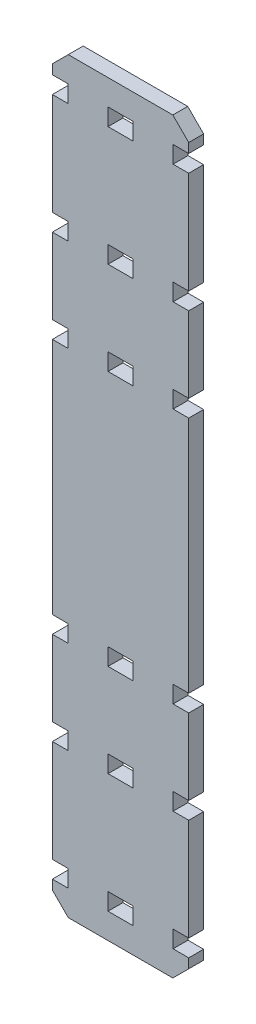
SolidWorks part; units mm, degrees
ref_plane "Front" through (0, 0, 0) normal (0, 0, 1) x (1, 0, 0)
ref_plane "Top" through (0, 0, 0) normal (0, 1, 0) x (1, 0, 0)
ref_plane "Right" through (0, 0, 0) normal (1, 0, 0) x (0, 0, -1)
ref_axis "side-side" through (80.9, 0, 0) along (-1, 0, 0)
ref_axis "up-down" through (0, 50, 0) along (0, -1, 0)
ref_axis "front-back" through (0, 0, -80.9) along (0, 0, 1)
sketch "Sketch1" plane through (0, 0, 0) normal (0, 0, 1) x (1, 0, 0)
  line L0 (21.7993, 111.361) -> (21.7993, 119.489) construction
  line L1 (43.5986, 119.489) -> (0, 119.489)
  line L2 (43.5986, 119.489) -> (43.5986, 111.361)
  line L3 (43.5986, -119.489) -> (0, -119.489)
  line L4 (0, 119.489) -> (0, 111.361)
  line L5 (25.7993, 111.361) -> (17.7993, 111.361)
  line L6 (5, 111.361) -> (-15, 111.361) construction
  line L7 (0, -111.361) -> (5, -111.361) construction
  line L8 (43.5986, 105.9) -> (38.5986, 105.9) construction
  line L9 (0, 111.361) -> (5, 111.361)
  line L10 (25.7993, 111.361) -> (25.7993, 105.9)
  line L11 (0, 105.9) -> (5, 105.9)
  line L12 (5, 111.361) -> (5, 105.9)
  line L13 (43.5986, 111.361) -> (38.5986, 111.361) construction
  line L14 (38.5986, 111.361) -> (43.5986, 111.361)
  line L15 (38.5986, 111.361) -> (38.5986, 105.9)
  line L16 (38.5986, 105.9) -> (43.5986, 105.9)
  line L17 (43.5986, 105.9) -> (43.5986, 73.261)
  line L18 (0, 105.9) -> (0, 73.261)
  line L19 (25.7993, 105.9) -> (17.7993, 105.9)
  line L20 (17.7993, 111.361) -> (17.7993, 105.9)
  line L21 (43.5986, 73.261) -> (38.5986, 73.261) construction
  line L22 (38.5986, 73.261) -> (43.5986, 73.261)
  line L23 (38.5986, 73.261) -> (38.5986, 67.8)
  line L24 (38.5986, 67.8) -> (43.5986, 67.8)
  line L25 (43.5986, 38.1) -> (43.5986, -38.1)
  line L26 (43.5986, 67.8) -> (38.5986, 67.8) construction
  line L27 (5, 73.261) -> (0, 73.261)
  line L28 (5, 73.261) -> (5, 67.8)
  line L29 (5, 67.8) -> (0, 67.8)
  line L31 (43.5986, 43.561) -> (38.5986, 43.561) construction
  line L32 (38.5986, 43.561) -> (43.5986, 43.561)
  line L33 (38.5986, 43.561) -> (38.5986, 38.1)
  line L34 (38.5986, 38.1) -> (43.5986, 38.1)
  line L35 (0, 67.8) -> (0, 43.561)
  line L36 (43.5986, 38.1) -> (38.5986, 38.1) construction
  line L37 (0, 43.561) -> (5, 43.561)
  line L39 (0, 38.1) -> (5, 38.1)
  line L40 (5, 43.561) -> (5, 38.1)
  line L41 (25.7993, 73.261) -> (17.7993, 73.261)
  line L42 (25.7993, 73.261) -> (25.7993, 67.8)
  line L43 (25.7993, 67.8) -> (17.7993, 67.8)
  line L44 (17.7993, 73.261) -> (17.7993, 67.8)
  line L45 (25.7993, 43.561) -> (17.7993, 43.561)
  line L46 (25.7993, 43.561) -> (25.7993, 38.1)
  line L47 (25.7993, 38.1) -> (17.7993, 38.1)
  line L48 (17.7993, 43.561) -> (17.7993, 38.1)
  line L49 (-15, -38.1) -> (5, -38.1) construction
  line L50 (38.5986, -38.1) -> (43.5986, -38.1)
  line L51 (38.5986, -38.1) -> (38.5986, -43.561)
  line L52 (38.5986, -43.561) -> (43.5986, -43.561)
  line L53 (0, -43.561) -> (0, -67.8)
  line L54 (-15, -67.8) -> (5, -67.8) construction
  line L55 (38.5986, -67.8) -> (43.5986, -67.8)
  line L56 (38.5986, -67.8) -> (38.5986, -73.261)
  line L57 (38.5986, -73.261) -> (43.5986, -73.261)
  line L58 (43.5986, -43.561) -> (43.5986, -67.8)
  line L59 (0, -105.9) -> (5, -105.9) construction
  line L60 (38.5986, -105.9) -> (43.5986, -105.9)
  line L61 (38.5986, -105.9) -> (38.5986, -111.361)
  line L62 (38.5986, -111.361) -> (43.5986, -111.361)
  line L63 (43.5986, -73.261) -> (43.5986, -105.9)
  line L64 (-15, -43.561) -> (5, -43.561) construction
  line L65 (5, -105.9) -> (0, -105.9)
  line L66 (5, -105.9) -> (5, -111.361)
  line L67 (5, -111.361) -> (0, -111.361)
  line L68 (0, -73.261) -> (0, -105.9)
  line L69 (5, -67.8) -> (0, -67.8)
  line L70 (5, -67.8) -> (5, -73.261)
  line L71 (5, -73.261) -> (0, -73.261)
  line L72 (43.5986, -111.361) -> (43.5986, -119.489)
  line L73 (5, -38.1) -> (0, -38.1)
  line L74 (5, -38.1) -> (5, -43.561)
  line L75 (5, -43.561) -> (0, -43.561)
  line L76 (43.5986, 67.8) -> (43.5986, 43.561)
  line L77 (25.7993, -38.1) -> (17.7993, -38.1)
  line L78 (25.7993, -38.1) -> (25.7993, -43.561)
  line L79 (25.7993, -43.561) -> (17.7993, -43.561)
  line L80 (17.7993, -38.1) -> (17.7993, -43.561)
  line L81 (-15, -73.261) -> (5, -73.261) construction
  line L82 (17.7993, -67.8) -> (25.7993, -67.8)
  line L83 (17.7993, -67.8) -> (17.7993, -73.261)
  line L84 (17.7993, -73.261) -> (25.7993, -73.261)
  line L85 (25.7993, -67.8) -> (25.7993, -73.261)
  line L86 (0, -111.361) -> (5, -111.361) construction
  line L87 (17.7993, -105.9) -> (25.7993, -105.9)
  line L88 (17.7993, -105.9) -> (17.7993, -111.361)
  line L89 (17.7993, -111.361) -> (25.7993, -111.361)
  line L90 (25.7993, -105.9) -> (25.7993, -111.361)
  line L91 (0, -111.361) -> (0, -119.489)
  line L92 (0, 38.1) -> (0, -38.1)
  point P17 (2.5, -111.361)
  dimension "D1" = 8.128
  dimension "D2" = 43.5986
  dimension "D3" = 8.128
  dimension "D4" = 5
  dimension "D5" = 8
extrude "Boss-Extrude1" add sketch "Sketch1" along normal blind 4.7625
chamfer "Chamfer1" distance 5.08 angle 45 4 edges at (43.5986, 119.489, 2.3813) (0, 119.489, 2.3813) (43.5986, -119.489, 2.3813) (0, -119.489, 2.3813)
